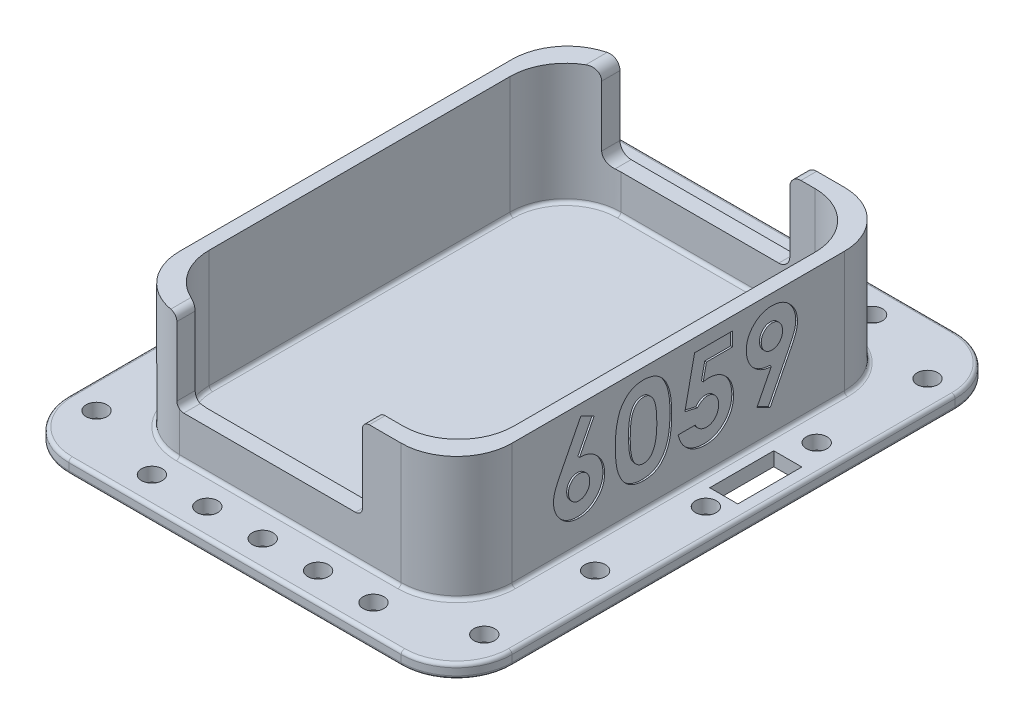
SolidWorks part; units mm, degrees
ref_plane "Front Plane" through (0, 0, 0) normal (0, 0, 1) x (1, 0, 0)
ref_plane "Top Plane" through (0, 0, 0) normal (0, 1, 0) x (1, 0, 0)
ref_plane "Right Plane" through (0, 0, 0) normal (1, 0, 0) x (0, 0, -1)
sketch "Sketch1" plane through (0, 0, 0) normal (0, 1, 0) x (1, 0, 0)
  line L1 (-38.1, -50.8) -> (38.1, -50.8)
  line L2 (-38.1, -50.8) -> (-38.1, 50.8)
  line L3 (-38.1, 50.8) -> (38.1, 50.8)
  line L4 (38.1, -50.8) -> (38.1, 50.8)
  line L5 (-38.1, -50.8) -> (38.1, 50.8) construction
  line L6 (-38.1, 50.8) -> (38.1, -50.8) construction
  point P0 (0, 0)
  dimension "D1" = 76.2
  dimension "D2" = 101.6
extrude "Boss-Extrude1" add sketch "Sketch1" along normal blind 0.7937
sketch "Sketch2" plane through (0, 0.7937, 0) normal (0, 1, 0) x (1, 0, 0)
  line L0 (38.1, 50.8) -> (-38.1, 50.8) construction
  line L1 (-34.925, -47.1805) -> (34.925, -47.1805)
  line L2 (-34.925, -47.1805) -> (-34.925, 47.1805)
  line L3 (-34.925, 47.1805) -> (34.925, 47.1805)
  line L4 (34.925, -47.1805) -> (34.925, 47.1805)
  line L5 (-34.925, -47.1805) -> (34.925, 47.1805) construction
  line L6 (-34.925, 47.1805) -> (34.925, -47.1805) construction
  line L7 (-38.1, -50.8) -> (38.1, -50.8)
  line L8 (-38.1, -50.8) -> (-38.1, 50.8)
  line L9 (-38.1, 50.8) -> (38.1, 50.8)
  line L10 (38.1, -50.8) -> (38.1, 50.8)
  line L11 (-38.1, -50.8) -> (38.1, 50.8) construction
  line L12 (-38.1, 50.8) -> (38.1, -50.8) construction
  line L13 (-38.1, 50.8) -> (-38.1, -50.8) construction
  point P0 (0, 0)
  point P6 (0, 0)
  dimension "D1" = 69.85
  dimension "D2" = 94.361
extrude "Boss-Extrude2" add sketch "Sketch2" along normal blind 27.178
fillet "Fillet1" radius 12.7 8 edges at (38.1, 13.9859, 50.8) (-38.1, 13.9859, 50.8) (-38.1, 13.9859, -50.8) (38.1, 13.9859, -50.8) (34.925, 14.3827, 47.1805) (-34.925, 14.3827, 47.1805) (34.925, 14.3827, -47.1805) (-34.925, 14.3827, -47.1805)
sketch "Sketch3" plane through (0, 0, 50.8) normal (0, 0, 1) x (1, 0, 0)
  line L1 (16.51, 27.9718) -> (-26.035, 27.9717)
  line L2 (16.51, 27.9718) -> (16.51, 9.525)
  line L3 (16.51, 9.525) -> (-26.035, 9.525)
  line L4 (-26.035, 27.9717) -> (-26.035, 9.525)
  line L5 (16.51, 27.9718) -> (-26.035, 9.525) construction
  line L6 (16.51, 9.525) -> (-26.035, 27.9717) construction
  line L8 (-38.1, 0) -> (-38.1, 27.9718) construction
  line L9 (-25.4, 27.9718) -> (25.4, 27.9718) construction
  line L10 (-25.4, 0) -> (25.4, 0) construction
  point P0 (-4.7625, 18.7484)
  dimension "D1" = 9.525
  dimension "D3" = 42.545
  dimension "D4" = 12.065
extrude "Cut-Extrude1" cut sketch "Sketch3" against normal through all
sketch "Sketch4" plane through (0, 27.9718, 0) normal (0, 1, 0) x (1, 0, 0)
  line L0 (25.4, 50.8) -> (16.51, 50.8) construction
  line L1 (-25.4, -50.8) -> (25.4, -50.8)
  line L2 (-38.1, -38.1) -> (-38.1, 38.1)
  line L3 (-25.4, 50.8) -> (25.4, 50.8)
  line L4 (38.1, -38.1) -> (38.1, 38.1)
  line L5 (-38.1, -50.8) -> (38.1, 50.8) construction
  line L6 (-38.1, 50.8) -> (38.1, -50.8) construction
  line L7 (38.1, -38.1) -> (38.1, 38.1) construction
  line L8 (22.225, 47.1805) -> (16.51, 47.1805) construction
  line L9 (-22.225, -47.1805) -> (22.225, -47.1805)
  line L10 (-34.925, -34.4805) -> (-34.925, 34.4805)
  line L11 (-22.225, 47.1805) -> (22.225, 47.1805)
  line L12 (34.925, -34.4805) -> (34.925, 34.4805)
  line L13 (-34.925, -47.1805) -> (34.925, 47.1805) construction
  line L14 (-34.925, 47.1805) -> (34.925, -47.1805) construction
  line L15 (34.925, -34.4805) -> (34.925, 34.4805) construction
  line L16 (-34.671, -34.4805) -> (-34.671, 34.4805)
  line L17 (-22.225, 46.9265) -> (22.225, 46.9265)
  line L18 (34.671, -34.4805) -> (34.671, 34.4805)
  line L19 (-22.225, -46.9265) -> (22.225, -46.9265)
  line L20 (-26.035, -50.7841) -> (-26.035, -46.5955)
  line L21 (16.51, -50.8) -> (16.51, -46.9265)
  line L22 (-26.035, -35.1709) -> (-26.035, -34.7133)
  line L23 (-26.035, 46.5955) -> (-26.035, 50.7841)
  line L24 (-26.035, 34.7133) -> (-26.035, 35.1709)
  arc A0 (-34.925, -34.4805) -> (-22.225, -47.1805) centre (-22.225, -34.4805) ccw
  arc A1 (22.225, -47.1805) -> (34.925, -34.4805) centre (22.225, -34.4805) ccw
  arc A2 (34.925, 34.4805) -> (22.225, 47.1805) centre (22.225, 34.4805) ccw
  arc A3 (-22.225, 47.1805) -> (-34.925, 34.4805) centre (-22.225, 34.4805) ccw
  arc A4 (-22.225, 46.9265) -> (-34.671, 34.4805) centre (-22.225, 34.4805) ccw
  arc A5 (34.671, 34.4805) -> (22.225, 46.9265) centre (22.225, 34.4805) ccw
  arc A6 (22.225, -46.9265) -> (34.671, -34.4805) centre (22.225, -34.4805) ccw
  arc A7 (-34.671, -34.4805) -> (-22.225, -46.9265) centre (-22.225, -34.4805) ccw
  arc A8 (-38.1, -38.1) -> (-25.4, -50.8) centre (-25.4, -38.1) ccw
  arc A9 (25.4, -50.8) -> (38.1, -38.1) centre (25.4, -38.1) ccw
  arc A10 (38.1, 38.1) -> (25.4, 50.8) centre (25.4, 38.1) ccw
  arc A11 (-25.4, 50.8) -> (-38.1, 38.1) centre (-25.4, 38.1) ccw
  point P0 (0, 0)
  point P10 (0, 0)
  line M4 (22.225, -47.1805) -> (16.51, -47.1805)
  line M5 (16.51, -47.1805) -> (16.51, -50.8)
  line M6 (16.51, -50.8) -> (25.4, -50.8)
  arc M7 (25.4, -50.8) -> (38.1, -38.1) centre (25.4, -38.1) ccw
  line M8 (38.1, -38.1) -> (38.1, 38.1)
  arc M9 (38.1, 38.1) -> (25.4, 50.8) centre (25.4, 38.1) ccw
  line M10 (25.4, 50.8) -> (16.51, 50.8)
  line M18 (16.51, 47.1805) -> (22.225, 47.1805)
  arc M19 (22.225, 47.1805) -> (34.925, 34.4805) centre (22.225, 34.4805) cw
  line M20 (34.925, 34.4805) -> (34.925, -34.4805)
  arc M21 (34.925, -34.4805) -> (22.225, -47.1805) centre (22.225, -34.4805) cw
  line M54 (16.51, 50.8) -> (16.51, 47.1805)
  dimension "D1" = 12.7
  dimension "D3" = 12.7
  dimension "D2" = 0.254
extrude "Boss-Extrude3" add sketch "Sketch4" along normal blind 0.508 contours M9 M10 M54 M18 M19 M20 M21 M4 M5 M6 M7 M8 | L23 A11 L2 A8 L20 A0 L10 A3 region at (17.5487, 27.9718, 48.9903) region at (-34.9786, 27.9718, 0)
fillet "Fillet2" radius 1.5875 4 edges at (16.51, 28.4798, 48.9902) (16.51, 9.525, 48.9902) (-26.035, 9.525, 48.6898) (-26.035, 28.4798, 48.6898)
sketch "Sketch5" plane through (0, 0, 0) normal (0, -1, 0) x (1, 0, 0)
  line L1 (50.8, -63.5) -> (-50.8, -63.5)
  line L2 (50.8, -63.5) -> (50.8, 63.5)
  line L3 (50.8, 63.5) -> (-50.8, 63.5)
  line L4 (-50.8, -63.5) -> (-50.8, 63.5)
  line L5 (50.8, -63.5) -> (-50.8, 63.5) construction
  line L6 (50.8, 63.5) -> (-50.8, -63.5) construction
  point P0 (0, 0)
  dimension "D1" = 127
  dimension "D2" = 101.6
extrude "Boss-Extrude4" add sketch "Sketch5" along normal blind 3.175
fillet "Fillet3" radius 12.7 4 edges at (-50.8, -1.5875, -63.5) (50.8, -1.5875, -63.5) (50.8, -1.5875, 63.5) (-50.8, -1.5875, 63.5)
sketch "Sketch7" plane through (0, 0, 0) normal (0, 1, 0) x (1, 0, 0)
  line L0 (-38.1, 63.5) -> (38.1, 63.5) construction
  line L1 (-50.8, -50.8) -> (-50.8, 50.8) construction
  line L2 (50.8, 50.8) -> (50.8, -50.8) construction
  line L3 (38.1, -63.5) -> (-38.1, -63.5) construction
  point P0 (-25.4, 57.15)
  point P1 (0, 57.15)
  point P2 (25.4, 57.15)
  point P3 (12.7, 57.15)
  point P4 (-12.7, 57.15)
  point P5 (-44.45, 50.8)
  point P6 (-44.45, 25.4)
  point P7 (-44.45, 0)
  point P8 (-44.45, -25.4)
  point P9 (-44.45, -50.8)
  point P10 (-25.4, -57.15)
  point P11 (0, -57.15)
  point P12 (25.4, -57.15)
  point P13 (12.7, -57.15)
  point P14 (-12.7, -57.15)
  point P15 (44.45, -50.8)
  point P16 (44.45, -25.4)
  point P17 (44.45, 0)
  point P18 (44.45, 25.4)
  point P19 (44.45, 50.8)
  dimension "D1" = 6.35
  dimension "D2" = 6.35
  dimension "D3" = 6.35
  dimension "D4" = 6.35
  dimension "D5" = 25.4
  dimension "D6" = 25.4
  dimension "D7" = 25.4
  dimension "D8" = 25.4
  dimension "D9" = 12.7
  dimension "D10" = 12.7
  dimension "D11" = 12.7
  dimension "D12" = 12.7
hole_wizard "3/16 (0.1875) Diameter Hole1" positions "3DSketch1" profile "Sketch8" hole size "3/16" standard "ANSI Inch" end condition through all
sketch3d "3DSketch1"
  point P0 (-44.45, 0, 50.8)
  point P3 (-44.45, 0, 25.4)
  point P6 (-44.45, 0, 0)
  point P9 (-44.45, 0, -25.4)
  point P12 (-44.45, 0, -50.8)
  point P15 (-25.4, 0, 57.15)
  point P18 (-12.7, 0, 57.15)
  point P21 (0, 0, 57.15)
  point P24 (12.7, 0, 57.15)
  point P27 (25.4, 0, 57.15)
  point P30 (44.45, 0, 50.8)
  point P33 (44.45, 0, 25.4)
  point P36 (44.45, 0, 0)
  point P39 (44.45, 0, -25.4)
  point P42 (44.45, 0, -50.8)
  point P45 (25.4, 0, -57.15)
  point P48 (12.7, 0, -57.15)
  point P50 (0, 0, -57.15)
  point P53 (-12.7, 0, -57.15)
  point P56 (-25.4, 0, -57.15)
sketch "Sketch8" plane through (-44.45, 0, 50.8) normal (1, 0, 0) x (0, 0, 1)
  line L0 (0, 0) -> (0, 3.175)
  line L1 (0, 3.175) -> (2.3812, 3.175)
  line L2 (2.3812, 3.175) -> (2.3812, 0)
  line L5 (2.3812, 0) -> (0, 0)
  line L11 (0, -6.35) -> (0, 107.95) construction
  dimension "Thru Hole Dia." = 4.7625
  dimension "Thru Hole Depth" = 3.175
fillet "Fillet4" radius 0.7937 8 edges at (-34.3803, 0, -47.0803) (0, 0, -50.8) (34.3803, 0, -47.0803) (38.1, 0, 0) (34.3803, 0, 47.0803) (0, 0, 50.8) (-34.3803, 0, 47.0803) (-38.1, 0, 0)
fillet "Fillet5" radius 0.7937 16 edges at (47.0803, -3.175, 59.7803) (50.8, -3.175, 0) (47.0803, -3.175, -59.7803) (0, -3.175, -63.5) (-47.0803, -3.175, -59.7803) (-50.8, -3.175, 0) (-47.0803, -3.175, 59.7803) (47.0803, 0, 59.7803) (50.8, 0, 0) (47.0803, 0, -59.7803) (0, 0, -63.5) (-47.0803, 0, -59.7803) (-50.8, 0, 0) (-47.0803, 0, 59.7803) (0, -3.175, 63.5) (0, 0, 63.5)
sketch "Sketch9" plane through (-38.1, 0, 0) normal (-1, 0, 0) x (0, 0, 1)
  text T0 "6059 " font "Century Gothic" height 19.05
extrude "Cut-Extrude2" cut sketch "Sketch9" against normal blind 0.3969
sketch "Sketch10" plane through (38.1, 0, 0) normal (1, 0, 0) x (0, 0, -1)
  text T0 "6059 " font "Century Gothic" height 19.05
extrude "Cut-Extrude3" cut sketch "Sketch10" against normal blind 0.3969
fillet "Fillet7" radius 0.7937 8 edges at (31.2053, 0.7937, 43.4608) (0, 0.7937, 47.1805) (-31.2053, 0.7937, 43.4608) (-34.925, 0.7937, 0) (-31.2053, 0.7937, -43.4608) (0, 0.7937, -47.1805) (31.2053, 0.7937, -43.4608) (34.925, 0.7937, 0)
sketch "Sketch11" plane through (0, 0, 0) normal (0, 1, 0) x (1, 0, 0)
  line L0 (0, 57.15) -> (0, 6.1431)
  line L1 (-41.1287, 4.1953) -> (-47.5714, 4.1953)
  line L2 (-47.5714, 4.1953) -> (-47.5714, 18.8787)
  line L3 (-47.5714, 18.8787) -> (-41.1287, 18.8787)
  line L4 (-41.1287, 18.8787) -> (-41.1287, 4.1953)
  line L5 (47.5714, 18.8787) -> (41.1287, 18.8787)
  line L6 (47.5714, 4.1953) -> (47.5714, 18.8787)
  line L7 (41.1287, 4.1953) -> (47.5714, 4.1953)
  line L8 (41.1287, 18.8787) -> (41.1287, 4.1953)
extrude "Cut-Extrude4" cut sketch "Sketch11" against normal blind 25.4 contours L5 L8 L7 L6 | L4 L3 L2 L1 region at (-44.35, 0, -11.537) region at (44.35, 0, -11.537)
sketch "Sketch13" plane through (0, 0, -47.1805) normal (0, 0, 1) x (1, 0, 0)
  line L2 (15.7833, 27.9718) -> (16.045, 9.99)
  line L3 (16.045, 9.99) -> (-21.0054, 10.3547)
  line L4 (-21.0054, 10.3547) -> (-21.0054, 27.9718)
  line L5 (-21.0054, 10.3547) -> (-21.0054, 36.4449)
  line L6 (-21.0054, 36.4449) -> (15.7833, 36.4449)
  line L7 (15.7833, 36.4449) -> (15.8656, 22.3199)
  arc A1 (14.9225, 9.525) -> (16.51, 11.1125) centre (14.9225, 11.1125) ccw construction
fillet "Fillet8" radius 2.54 4 edges at (16.51, 28.4798, -48.9902) (-26.035, 28.4798, -48.6898) (-26.035, 9.525, -48.6898) (16.51, 9.525, -48.9902)
